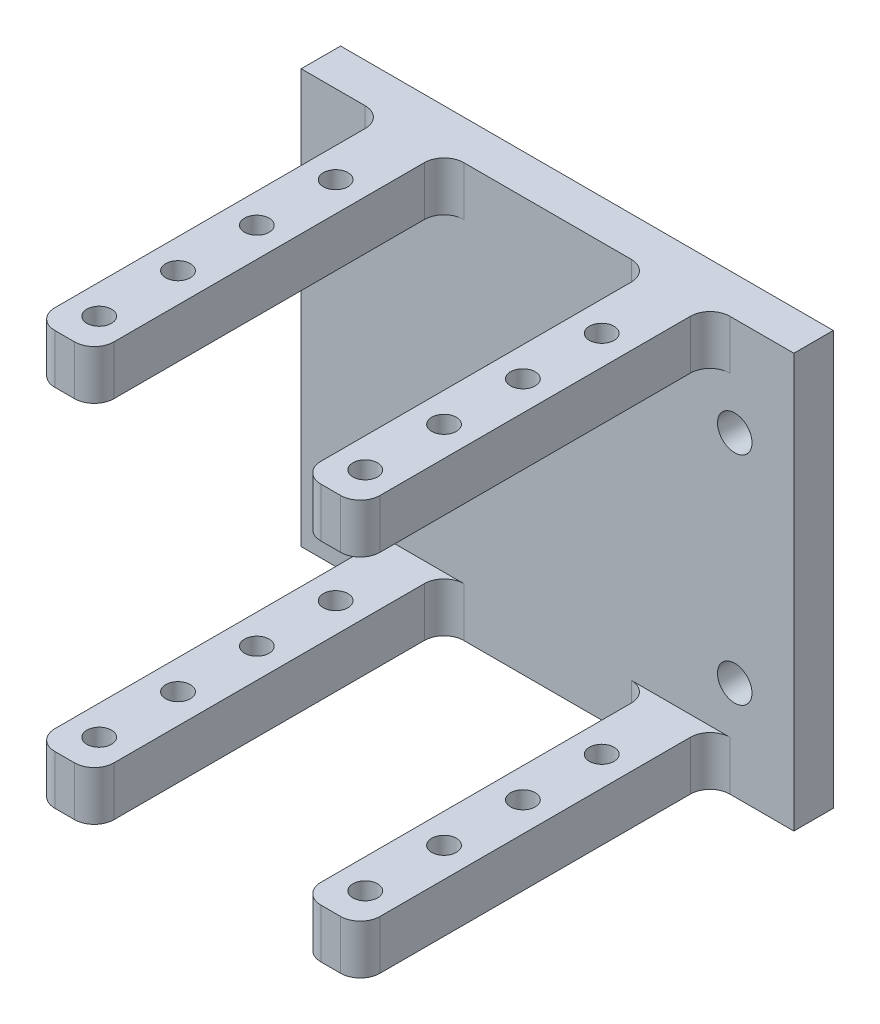
SolidWorks part; units mm, degrees
ref_plane "Plan de face" through (0, 0, 0) normal (0, 0, 1) x (1, 0, 0)
ref_plane "Plan de dessus" through (0, 0, 0) normal (0, 1, 0) x (1, 0, 0)
ref_plane "Plan de droite" through (0, 0, 0) normal (1, 0, 0) x (0, 0, -1)
sketch "Esquisse1" plane through (0, 0, 0) normal (0, 0, 1) x (1, 0, 0)
  line L1 (-25, -21) -> (25, -21)
  line L2 (-25, -21) -> (-25, 21)
  line L3 (-25, 21) -> (25, 21)
  line L4 (25, -21) -> (25, 21)
  line L5 (-25, -21) -> (25, 21) construction
  line L6 (-25, 21) -> (25, -21) construction
  line L7 (19, -11) -> (-19, -11) construction
  line L8 (19, -11) -> (19, 11) construction
  line L9 (19, 11) -> (-19, 11) construction
  line L10 (-19, -11) -> (-19, 11) construction
  line L11 (19, -11) -> (-19, 11) construction
  line L12 (19, 11) -> (-19, -11) construction
  circle A0 centre (-19, 11) radius 1.75
  circle A1 centre (19, 11) radius 1.75
  circle A2 centre (19, -11) radius 1.75
  circle A3 centre (-19, -11) radius 1.75
  point P0 (0, 0)
  point P6 (0, 0)
  dimension "D5" = 3.5
  dimension "D1" = 42
  dimension "D2" = 50
  dimension "D3" = 38
  dimension "D4" = 22
extrude "Boss.-Extru.1" add sketch "Esquisse1" along normal blind 4
sketch "Esquisse2" plane through (0, 0, 4) normal (0, 0, 1) x (1, 0, 0)
  line L0 (25, 21) -> (-25, 21) construction
  line L1 (-16.5, 21) -> (-10.5, 21)
  line L2 (-16.5, 21) -> (-16.5, 16)
  line L3 (-16.5, 16) -> (-10.5, 16)
  line L4 (-10.5, 21) -> (-10.5, 16)
  line L5 (-10.5, 21) -> (0, 21) construction
  line L6 (16.5, 21) -> (10.5, 21)
  line L7 (16.5, 21) -> (16.5, 16)
  line L8 (16.5, 16) -> (10.5, 16)
  line L9 (10.5, 21) -> (10.5, 16)
  line L10 (0, 21) -> (10.5, 21) construction
  line L11 (0, 21) -> (0, 0) construction
  line L12 (0, 0) -> (4.2364, 0) construction
  line L13 (-16.5, -21) -> (-16.5, -16)
  line L14 (-16.5, -21) -> (-10.5, -21)
  line L15 (-10.5, -21) -> (-10.5, -16)
  line L16 (-16.5, -16) -> (-10.5, -16)
  line L17 (16.5, -21) -> (16.5, -16)
  line L18 (16.5, -21) -> (10.5, -21)
  line L19 (10.5, -21) -> (10.5, -16)
  line L20 (16.5, -16) -> (10.5, -16)
  dimension "D1" = 21
  dimension "D2" = 6
  dimension "D3" = 5
extrude "Boss.-Extru.2" add sketch "Esquisse2" along normal blind 35.5
sketch "Esquisse3" plane through (0, 21, 0) normal (0, 1, 0) x (1, 0, 0)
  line L0 (-13.5, -39.5) -> (-13.5, -4) construction
  line L1 (-10.5, -39.5) -> (-16.5, -39.5) construction
  line L2 (10.5, -4) -> (-10.5, -4) construction
  line L3 (0, 0) -> (0, -7.3093) construction
  line L4 (25, 0) -> (-25, 0) construction
  circle A0 centre (-13.5, -12) radius 1.25
  circle A1 centre (-13.5, -20) radius 1.25
  circle A2 centre (-13.5, -28) radius 1.25
  circle A3 centre (-13.5, -36) radius 1.25
  circle A4 centre (13.5, -36) radius 1.25
  circle A5 centre (13.5, -28) radius 1.25
  circle A6 centre (13.5, -20) radius 1.25
  circle A7 centre (13.5, -12) radius 1.25
  dimension "D3" = 38
  dimension "D2" = 2.5
  dimension "D1" = 8
extrude "Enlèv. mat.-Extru.1" cut sketch "Esquisse3" against normal through all
fillet "Congé1" radius 2 16 edges at (-16.5, -18.5, 39.5) (-16.5, 18.5, 39.5) (16.5, -18.5, 39.5) (16.5, 18.5, 39.5) (10.5, -18.5, 4) (16.5, -18.5, 4) (-10.5, -18.5, 4) (-16.5, -18.5, 4) (-16.5, 18.5, 4) (-10.5, 18.5, 4) (10.5, 18.5, 4) (16.5, 18.5, 4) (-10.5, -18.5, 39.5) (10.5, -18.5, 39.5) (10.5, 18.5, 39.5) (-10.5, 18.5, 39.5)
